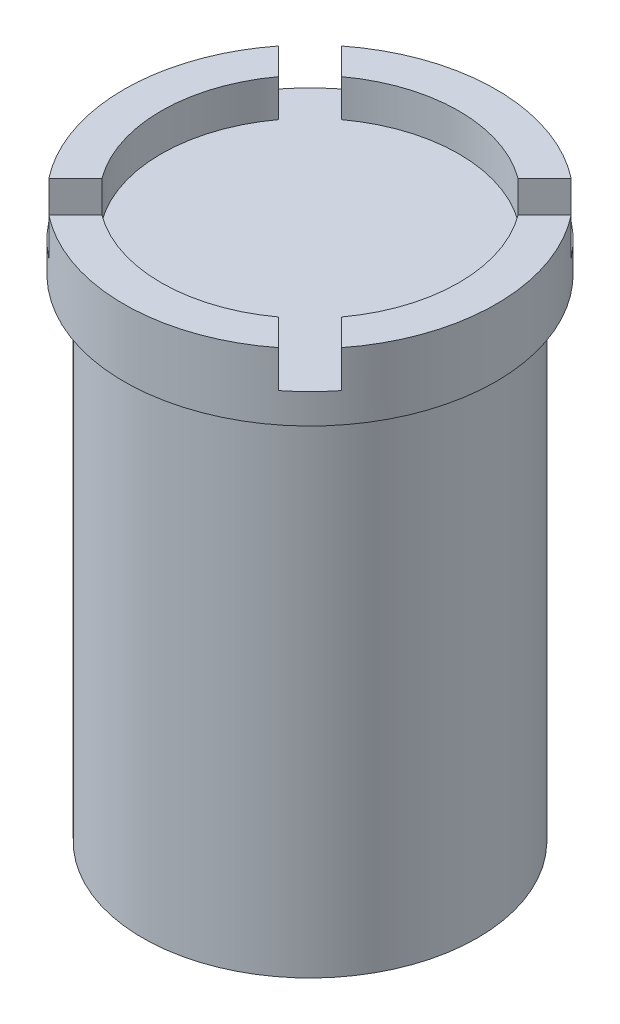
SolidWorks part; units mm, degrees
ref_plane "Front Plane" through (0, 0, 0) normal (0, 0, 1) x (1, 0, 0)
ref_plane "Top Plane" through (0, 0, 0) normal (0, 1, 0) x (1, 0, 0)
ref_plane "Right Plane" through (0, 0, 0) normal (1, 0, 0) x (0, 0, -1)
sketch "Body Block Sketch" plane through (0, 0, 0) normal (0, 0, 1) x (1, 0, 0)
  line L1 (0, 0) -> (400, 0)
  line L2 (0, 0) -> (0, -1400)
  line L3 (0, -1400) -> (450, -1400)
  line L6 (450, 0) -> (450, -80) construction
  line L9 (500, 0) -> (500, 100)
  line L13 (500, 100) -> (400, 100)
  line L14 (400, 0) -> (400, 100)
  line L15 (400, 0) -> (450, 0) construction
  line L16 (450, 0) -> (400, 0) construction
  line L17 (450, -80) -> (450, -1400)
  line L18 (450, -80) -> (500, -80)
  line L19 (500, 0) -> (500, -80)
  line L21 (400, 0) -> (500, 0) construction
  dimension "D1" = 1400
  dimension "D2" = 500
  dimension "D3" = 50
  dimension "D4" = 100
  dimension "D5" = 100
  dimension "D6" = 80
revolve "Body Block Revolve" add sketch "Body Block Sketch" angle 360 about L2
sketch "Gripper Gap Sketch" plane through (0, 0, 0) normal (0, 1, 0) x (1, 0, 0)
  line L0 (0, 0) -> (0, 500) construction
  line L1 (311.127, 395.9798) -> (395.9798, 311.127)
  line L2 (311.127, 395.9798) -> (-42.4264, 42.4264)
  line L3 (-42.4264, 42.4264) -> (42.4264, -42.4264)
  line L4 (395.9798, 311.127) -> (42.4264, -42.4264)
  line L5 (0, 0) -> (353.5534, 353.5534) construction
  circle A0 centre (0, 0) radius 500 construction
  dimension "D1" = 120
  dimension "D2" = 500
  dimension "D3" = 45
extrude "Gripper Gap Cut" cut sketch "Gripper Gap Sketch" along normal up to surface (100 mm away) up to face at (-400, 100, 0)
pattern_circular "Gripper Gap Cut Propagation" count 4 over 360 about axis through (0, 0, 0) along (0, -1, 0) of "Gripper Gap Cut"
ref_plane "Gripper Lip Midplane" through (0, 50, 0) normal (0, 1, 0) x (1, 0, 0)
sketch "Gripper Gap Midpoint Sketch" plane through (0, 50, 0) normal (0, 1, 0) x (1, 0, 0)
  line L0 (353.5534, 353.5534) -> (282.8427, 282.8427) construction
  line L1 (282.8427, 282.8427) -> (0, 0) construction
  line L2 (0, 0) -> (353.5534, 353.5534) construction
  circle A0 centre (0, 0) radius 400 construction
  circle A1 centre (0, 0) radius 500 construction
  circle A2 centre (0, 0) radius 500 construction
  arc A3 (237.2162, 322.069) -> (-237.2162, 322.069) centre (0, 0) ccw construction
  point P11 (318.1981, 318.1981)
  point P14 (318.1981, 318.1981)
  point P18 (318.1981, -318.1981)
  point P19 (-318.1981, -318.1981)
  point P20 (-318.1981, 318.1981)
  point P21 (0, 0)
  dimension "D1" = 4
ref_point "Gripper Gap Midpoint Point"
